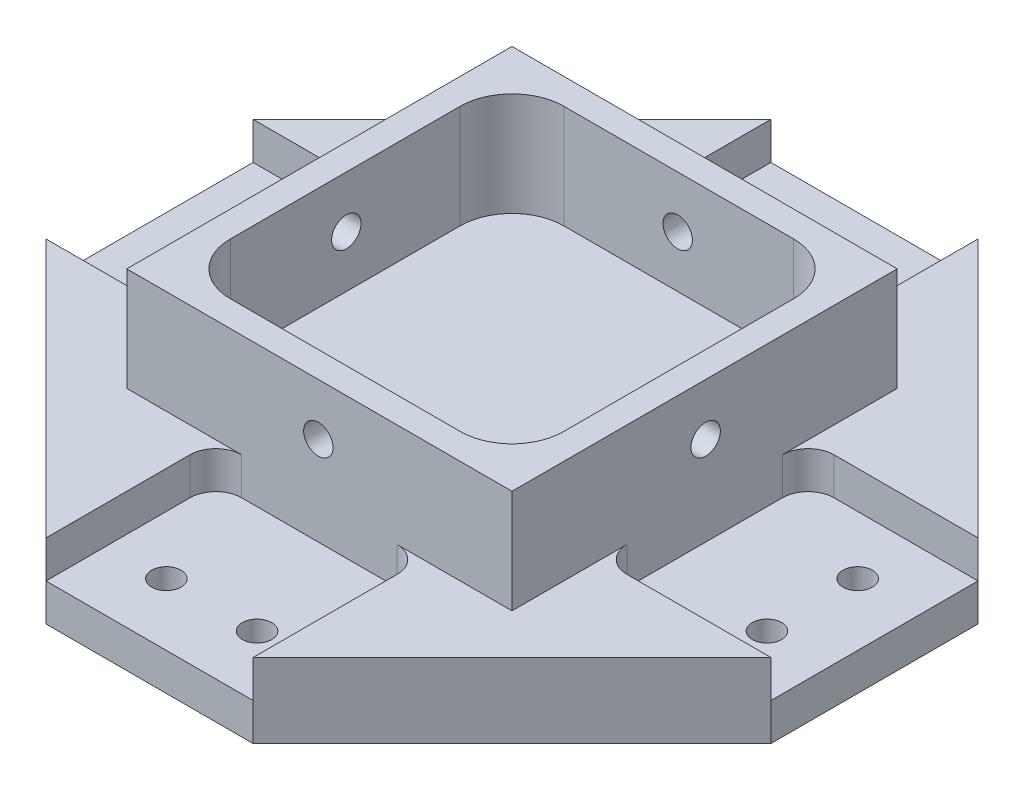
SolidWorks part; units mm, degrees
material "6061 Alloy"
ref_plane "Front Plane" through (0, 0, 0) normal (0, 0, 1) x (1, 0, 0)
ref_plane "Top Plane" through (0, 0, 0) normal (0, 1, 0) x (1, 0, 0)
ref_plane "Right Plane" through (0, 0, 0) normal (1, 0, 0) x (0, 0, -1)
sketch "Sketch1" plane through (0, 0, 0) normal (0, 1, 0) x (1, 0, 0)
  line L1 (0, 0) -> (88.9, 0)
  line L2 (0, 0) -> (0, 88.9)
  line L3 (0, 88.9) -> (88.9, 88.9)
  line L4 (88.9, 0) -> (88.9, 88.9)
  dimension "D1" = 88.9
  dimension "D2" = 88.9
extrude "Boss-Extrude1" add sketch "Sketch1" along normal blind 9.144
sketch "Sketch2" plane through (0, 9.144, 0) normal (0, 1, 0) x (1, 0, 0)
  line L0 (88.9, 88.9) -> (0, 88.9) construction
  line L1 (31.75, 88.9) -> (57.15, 88.9)
  line L2 (31.75, 88.9) -> (31.75, 67.31)
  line L3 (31.75, 67.31) -> (57.15, 67.31)
  line L4 (57.15, 88.9) -> (57.15, 67.31)
  line L5 (0, 88.9) -> (0, 0) construction
  line L6 (0, 57.15) -> (21.59, 57.15)
  line L7 (0, 57.15) -> (0, 31.75)
  line L8 (0, 31.75) -> (21.59, 31.75)
  line L9 (21.59, 57.15) -> (21.59, 31.75)
  line L10 (0, 0) -> (88.9, 0) construction
  line L11 (31.75, 0) -> (57.15, 0)
  line L12 (31.75, 0) -> (31.75, 21.59)
  line L13 (31.75, 21.59) -> (57.15, 21.59)
  line L14 (57.15, 0) -> (57.15, 21.59)
  line L15 (88.9, 0) -> (88.9, 88.9) construction
  line L16 (88.9, 57.15) -> (67.31, 57.15)
  line L17 (88.9, 57.15) -> (88.9, 31.75)
  line L18 (88.9, 31.75) -> (67.31, 31.75)
  line L19 (67.31, 57.15) -> (67.31, 31.75)
  dimension "D1" = 31.75
  dimension "D2" = 25.4
  dimension "D3" = 25.4
  dimension "D4" = 31.75
  dimension "D5" = 25.4
  dimension "D6" = 31.75
  dimension "D7" = 25.4
  dimension "D8" = 31.75
  dimension "D9" = 21.59
  dimension "D10" = 21.59
  dimension "D11" = 21.59
  dimension "D12" = 21.59
extrude "Cut-Extrude1" cut sketch "Sketch2" against normal blind 4.572
sketch "Sketch3" plane through (0, 9.144, 0) normal (0, 1, 0) x (1, 0, 0)
  line L0 (31.75, 88.9) -> (0, 88.9) construction
  line L1 (20.6375, 68.2625) -> (68.2625, 68.2625)
  line L2 (20.6375, 68.2625) -> (20.6375, 20.6375)
  line L3 (20.6375, 20.6375) -> (68.2625, 20.6375)
  line L4 (68.2625, 68.2625) -> (68.2625, 20.6375)
  line L5 (0, 31.75) -> (0, 0) construction
  line L6 (88.9, 31.75) -> (88.9, 57.15) construction
  line L7 (57.15, 88.9) -> (31.75, 88.9) construction
  line L8 (0, 57.15) -> (0, 31.75) construction
  line L9 (31.75, 0) -> (57.15, 0) construction
  circle A0 centre (28.194, 44.45) radius 2.4
  circle A1 centre (44.45, 60.706) radius 2.4
  circle A2 centre (60.706, 44.45) radius 2.4
  circle A3 centre (44.45, 28.194) radius 2.4
  dimension "D5" = 4.8
  dimension "D6" = 4.8
  dimension "D7" = 4.8
  dimension "D8" = 4.8
  dimension "D1" = 47.625
  dimension "D2" = 47.625
  dimension "D3" = 20.6375
  dimension "D4" = 20.6375
  dimension "D9" = 28.194
  dimension "D10" = 28.194
  dimension "D11" = 28.194
  dimension "D12" = 28.194
  dimension "D13" = 23.8125
  dimension "D14" = 23.8125
  dimension "D15" = 23.8125
  dimension "D16" = 23.8125
extrude "Cut-Extrude2" [suppressed] cut sketch "Sketch3" against normal through all contours A2 | A1 | A0 | A3
sketch "Sketch4" plane through (0, 4.572, 0) normal (0, 1, 0) x (1, 0, 0)
  line L0 (0, 57.15) -> (0, 31.75) construction
  line L1 (57.15, 88.9) -> (31.75, 88.9) construction
  line L2 (88.9, 31.75) -> (88.9, 57.15) construction
  line L3 (31.75, 0) -> (57.15, 0) construction
  line L4 (0, 31.75) -> (21.59, 31.75) construction
  line L5 (31.75, 21.59) -> (31.75, 0) construction
  line L6 (67.31, 31.75) -> (88.9, 31.75) construction
  line L7 (57.15, 67.31) -> (57.15, 88.9) construction
  circle A0 centre (81.28, 50.0126) radius 1.8034
  circle A1 centre (81.28, 38.8874) radius 1.8034
  circle A2 centre (50.0126, 81.28) radius 1.8034
  circle A3 centre (38.8874, 81.28) radius 1.8034
  circle A4 centre (7.62, 50.0126) radius 1.8034
  circle A5 centre (7.62, 38.8874) radius 1.8034
  circle A6 centre (38.8874, 7.62) radius 1.8034
  circle A7 centre (50.0126, 7.62) radius 1.8034
  dimension "D1" = 3.6068
  dimension "D2" = 3.6068
  dimension "D3" = 3.6068
  dimension "D4" = 3.6068
  dimension "D5" = 3.6068
  dimension "D6" = 3.6068
  dimension "D7" = 3.6068
  dimension "D8" = 3.6068
  dimension "D9" = 7.62
  dimension "D10" = 7.62
  dimension "D11" = 7.62
  dimension "D12" = 7.62
  dimension "D13" = 7.62
  dimension "D14" = 7.62
  dimension ".313" = 7.62
  dimension "D16" = 7.62
  dimension "D17" = 11.1252
  dimension "D18" = 7.1374
  dimension "D19" = 7.1374
  dimension "D20" = 11.1252
  dimension "D21" = 7.1374
  dimension "D22" = 11.1252
  dimension "D23" = 7.1374
  dimension "D24" = 11.1252
extrude "Cut-Extrude3" cut sketch "Sketch4" against normal through all
sketch "Sketch5" plane through (0, 9.144, 0) normal (0, 1, 0) x (1, 0, 0)
  line L0 (88.9, 88.9) -> (57.15, 88.9) construction
  line L1 (88.9, 31.75) -> (88.9, 57.15) construction
  circle A0 centre (44.45, 44.45) radius 6.35
  dimension "D1" = 12.7
  dimension "D2" = 44.45
  dimension "D3" = 44.45
extrude "Cut-Extrude4" [suppressed] cut sketch "Sketch5" against normal through all
sketch "Sketch6" plane through (0, 9.144, 0) normal (0, 1, 0) x (1, 0, 0)
  line L0 (88.9, 31.75) -> (57.15, 0)
  line L1 (57.15, 0) -> (88.9, 0)
  line L2 (88.9, 0) -> (88.9, 31.75)
extrude "Cut-Extrude5" cut sketch "Sketch6" against normal through all
sketch "Sketch7" plane through (0, 9.144, 0) normal (0, 1, 0) x (1, 0, 0)
  line L0 (0, 88.9) -> (0, 57.15) construction
  line L1 (20.828, 68.072) -> (68.072, 68.072)
  line L2 (20.828, 68.072) -> (20.828, 20.828)
  line L3 (20.828, 20.828) -> (68.072, 20.828)
  line L4 (68.072, 68.072) -> (68.072, 20.828)
  line L5 (0, 0) -> (31.75, 0) construction
  line L7 (24.003, 24.003) -> (64.897, 24.003)
  line L8 (24.003, 24.003) -> (24.003, 64.897)
  line L9 (24.003, 64.897) -> (64.897, 64.897)
  line L10 (64.897, 24.003) -> (64.897, 64.897)
  dimension "D1" = 47.244
  dimension "D2" = 47.244
  dimension "D3" = 20.828
  dimension "D4" = 20.828
  dimension "D5" = 3.175
  dimension "D6" = 3.175
  dimension "D7" = 3.175
  dimension "D8" = 3.175
extrude "Boss-Extrude2" add sketch "Sketch7" along normal blind 12.7 and the other way up to next (4.572 mm away)
fillet "Fillet9" radius 6.35 1 edges at (64.897, 15.494, -24.003)
fillet "Fillet10" radius 6.35 1 edges at (24.003, 15.494, -24.003)
fillet "Fillet11" radius 6.35 1 edges at (64.897, 15.494, -64.897)
fillet "Fillet12" radius 6.35 1 edges at (24.003, 15.494, -64.897)
fillet "Fillet15" radius 3.175 1 edges at (20.828, 6.858, -57.15)
fillet "Fillet16" radius 3.175 1 edges at (31.75, 6.858, -20.828)
fillet "Fillet17" radius 3.175 1 edges at (57.15, 6.858, -20.828)
fillet "Fillet18" radius 3.175 1 edges at (68.072, 6.858, -57.15)
fillet "Fillet19" radius 3.175 1 edges at (68.072, 6.858, -31.75)
fillet "Fillet20" radius 3.175 1 edges at (31.75, 6.858, -68.072)
fillet "Fillet21" radius 3.175 1 edges at (57.15, 6.858, -68.072)
fillet "Fillet22" radius 3.175 1 edges at (20.828, 6.858, -31.75)
sketch "Sketch9" plane through (0, 0, -68.072) normal (0, 0, -1) x (-1, 0, 0)
  line L0 (-68.072, 21.844) -> (-68.072, 9.144) construction
  line L1 (-68.072, 21.844) -> (-20.828, 21.844) construction
  circle A0 centre (-44.323, 15.494) radius 1.8034
  dimension "D1" = 3.6068
  dimension "D2" = 23.749
  dimension "D3" = 6.35
extrude "Cut-Extrude6" cut sketch "Sketch9" against normal through all
sketch "Sketch10" plane through (68.072, 0, 0) normal (1, 0, 0) x (0, 0, -1)
  line L0 (20.828, 21.844) -> (68.072, 21.844) construction
  line L1 (20.828, 21.844) -> (20.828, 9.144) construction
  circle A0 centre (44.577, 15.494) radius 1.8034
  dimension "D1" = 3.6068
  dimension "D2" = 6.35
  dimension "D3" = 23.749
extrude "Cut-Extrude7" cut sketch "Sketch10" against normal through all
sketch "Sketch12" plane through (0, 9.144, 0) normal (0, 1, 0) x (1, 0, 0)
  line L0 (0, 31.75) -> (31.75, 0)
  line L1 (31.75, 0) -> (0, 0)
  line L2 (0, 0) -> (0, 31.75)
  line L3 (57.15, 88.9) -> (88.9, 57.15)
  line L4 (88.9, 57.15) -> (88.9, 88.9)
  line L5 (88.9, 88.9) -> (57.15, 88.9)
  line L6 (0, 57.15) -> (31.75, 88.9)
  line L7 (31.75, 88.9) -> (0, 88.9)
  line L8 (0, 88.9) -> (0, 57.15)
sketch "Sketch14" plane through (0, 0, 0) normal (0, -1, 0) x (1, 0, 0)
  line L0 (60.2924, -60.2924) -> (28.8616, -28.8616) construction
  line L6 (24.003, -58.547) -> (24.003, -30.353) construction
  line L7 (30.353, -24.003) -> (58.547, -24.003) construction
  circle A0 centre (28.8616, -28.8616) radius 2.5797
  circle A1 centre (60.2924, -60.2924) radius 2.5797
  point P0 (44.577, -44.577)
  dimension "D1" = 44.45
  dimension "D2" = 5.1594
  dimension "D3" = 5.1594
  dimension "D4" = 20.574
  dimension "D5" = 20.574
extrude "Cut-Extrude9" cut sketch "Sketch14" against normal through all
extrude "Cut-Extrude10" cut sketch "Sketch12" against normal through all
equation "\"hinge_hole\"= 0.142in"
equation "\"D1@Sketch4\"=\"hinge_hole\""
equation "\"D2@Sketch4\"=\"hinge_hole\""
equation "\"D3@Sketch4\"=\"hinge_hole\""
equation "\"D4@Sketch4\"=\"hinge_hole\""
equation "\"D5@Sketch4\"=\"hinge_hole\""
equation "\"D6@Sketch4\"=\"hinge_hole\""
equation "\"D7@Sketch4\"=\"hinge_hole\""
equation "\"D8@Sketch4\"=\"hinge_hole\""
equation "\"hinge_hole_dist\"= 0.297 + 0.25"
equation "\".313@Sketch4\"=.3"
equation "\"hinge_hole_sep\"=0.438"
equation "\"hinge_hole_from_wall\"= ( 1 - \"hinge_hole_sep\" ) / 2"
equation "\"D17@Sketch4\"=\"hinge_hole_sep\""
equation "\"D18@Sketch4\"=\"hinge_hole_from_wall\""
equation "\"D19@Sketch4\"=\"hinge_hole_from_wall\""
equation "\"D20@Sketch4\"=\"hinge_hole_sep\""
equation "\"D21@Sketch4\"=\"hinge_hole_from_wall\""
equation "\"D22@Sketch4\"=\"hinge_hole_sep\""
equation "\"D23@Sketch4\"=\"hinge_hole_from_wall\""
equation "\"D24@Sketch4\"=\"hinge_hole_sep\""
equation "\"D9@Sketch2\"=\"hinge_hole_dist\" + (0.6-0.297)"
equation "\"D12@Sketch2\"=\"hinge_hole_dist\" + (0.6-0.297)"
equation "\"D11@Sketch2\"=\"hinge_hole_dist\" + (0.6-0.297)"
equation "\"D10@Sketch2\"=\"hinge_hole_dist\" + (0.6-0.297)"
